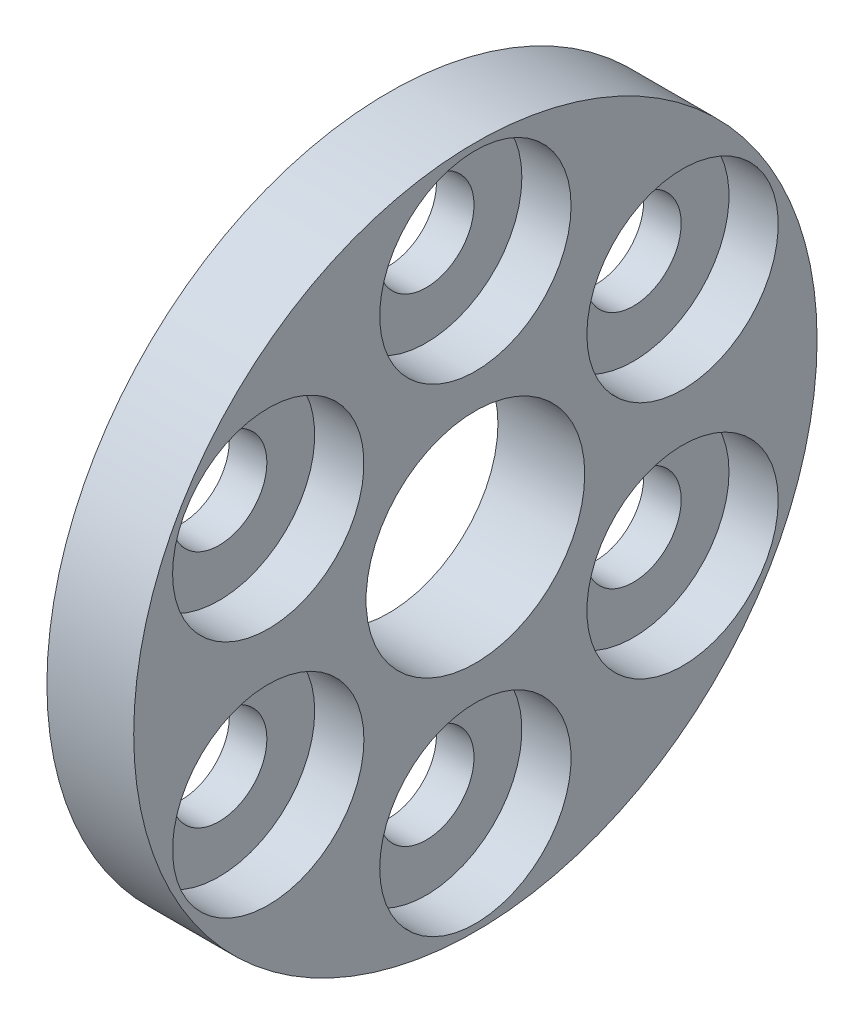
SolidWorks part; units mm, degrees
material "1023 Carbon Steel Sheet (SS)"
ref_plane "Front Plane" through (0, 0, 0) normal (0, 0, 1) x (1, 0, 0)
ref_plane "Top Plane" through (0, 0, 0) normal (0, 1, 0) x (1, 0, 0)
ref_plane "Right Plane" through (0, 0, 0) normal (1, 0, 0) x (0, 0, -1)
sketch "Sketch1" plane through (0, 0, 0) normal (1, 0, 0) x (0, 0, -1)
  circle A0 centre (0, 0) radius 12.5
  dimension "D1" = 25
extrude "Boss-Extrude1" add sketch "Sketch1" along normal blind 3.175
sketch "Sketch2" plane through (3.175, 0, 0) normal (1, 0, 0) x (0, 0, -1)
  circle A0 centre (0, 8.75) radius 1.75
  point P2 (0, 0)
  dimension "D1" = 3.5
  dimension "D2" = 8.75
sketch "Sketch3" plane through (3.175, 0, 0) normal (1, 0, 0) x (0, 0, -1)
  circle A0 centre (0, 0) radius 4
  dimension "D1" = 8
extrude "Cut-Extrude1" cut sketch "Sketch3" against normal through all
extrude "Cut-Extrude2" cut sketch "Sketch2" against normal through all
sketch "Sketch4" plane through (3.175, 0, 0) normal (1, 0, 0) x (0, 0, -1)
  line L1 (1.5877, 11.5) -> (-1.5877, 11.5)
  line L2 (-1.5877, 11.5) -> (-3.1754, 8.75)
  line L3 (-3.1754, 8.75) -> (-1.5877, 6)
  line L4 (-1.5877, 6) -> (1.5877, 6)
  line L5 (1.5877, 6) -> (3.1754, 8.75)
  line L6 (3.1754, 8.75) -> (1.5877, 11.5)
  circle A0 centre (0, 8.75) radius 2.75 construction
  circle A1 centre (0, 8.75) radius 3.5
  circle M13 centre (0, 8.75) radius 1.75
  dimension "D2" = 7
  dimension "D1" = 5.5
extrude "Cut-Extrude3" cut sketch "Sketch4" against normal blind 1.8 contours L5 L6 L1 L2 L3 L4 M13 | A1 L6 L5 L4 L3 L2 L1 | M13 | L1 L2 L3 L4 L5 L6 | A1 region at (3.175, 10.083, -2.3088) region at (3.175, 8.75, 3.401) region at (3.175, 8.75, 0)
pattern_circular "CirPattern3" count 6 over 360 about axis through (0, 0, 0) along (1, 0, 0) of "Cut-Extrude3", "Cut-Extrude2" reverse direction yes
